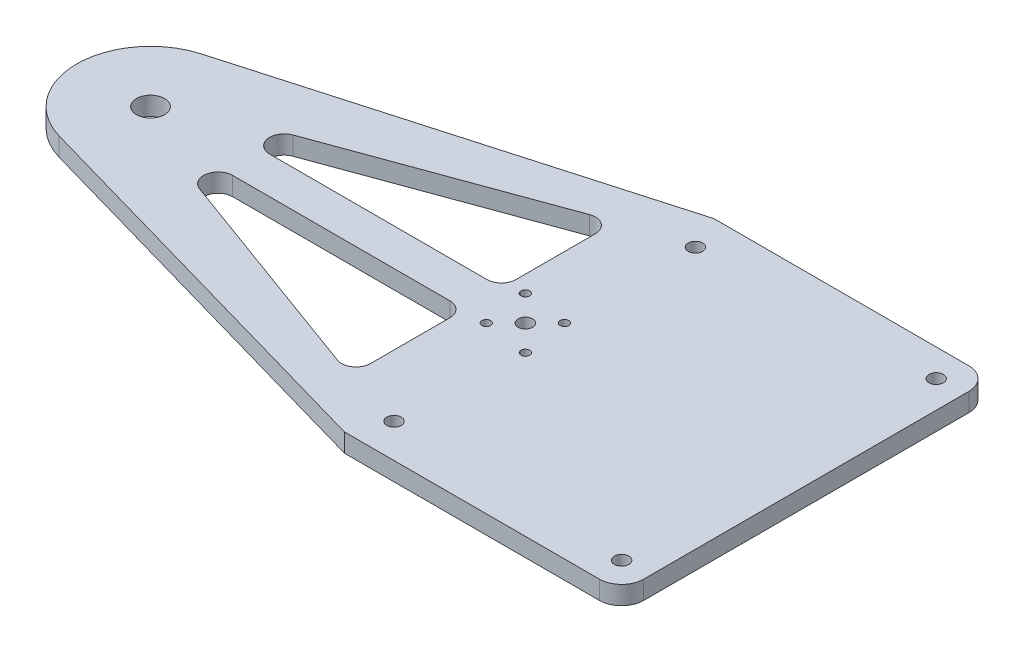
SolidWorks part; units mm, degrees
material "UHMW"
ref_plane "Front Plane" through (0, 0, 0) normal (0, 0, 1) x (1, 0, 0)
ref_plane "Top Plane" through (0, 0, 0) normal (0, 1, 0) x (1, 0, 0)
ref_plane "Right Plane" through (0, 0, 0) normal (1, 0, 0) x (0, 0, -1)
sketch "Sketch1" plane through (0, 0, 0) normal (0, 1, 0) x (1, 0, 0)
  line L0 (-47.625, 0) -> (47.625, 0) construction
  line L1 (-47.625, -63.5) -> (47.625, -63.5)
  line L2 (-47.625, -63.5) -> (-47.625, 63.5)
  line L3 (-47.625, 63.5) -> (47.625, 63.5)
  line L4 (47.625, -63.5) -> (47.625, 63.5)
  line L5 (-47.625, -63.5) -> (47.625, 63.5) construction
  line L6 (-47.625, 63.5) -> (47.625, -63.5) construction
  point P0 (0, 0)
  dimension "D1" = 95.25
  dimension "D2" = 127
  dimension "D3" = 63.5
extrude "Boss-Extrude1" add sketch "Sketch1" along normal blind 6.35
sketch "Sketch4" plane through (0, 6.35, 0) normal (0, 1, 0) x (1, 0, 0)
  line L1 (-47.625, 63.5) -> (-184.7599, 24.4278)
  line L5 (-47.625, 63.5) -> (-47.625, -63.5) construction
  line L9 (-47.625, -63.5) -> (-184.7599, -24.4278)
  line L10 (-47.625, 63.5) -> (-47.625, -63.5)
  arc A0 (-184.7599, 24.4278) -> (-184.7599, -24.4278) centre (-177.8, 0) ccw
  dimension "D1" = 50.8
  dimension "D2" = 177.8
extrude "Boss-Extrude3" add sketch "Sketch4" against normal blind 6.35
sketch "Sketch5" plane through (0, 6.35, 0) normal (0, 1, 0) x (1, 0, 0)
  line L0 (-48.9458, 0) -> (-31.7264, 0) construction
  line L3 (-48.9458, 0) -> (-91.3931, 0) construction
  circle A0 centre (-177.8, 0) radius 4.826
  circle A1 centre (-48.9458, 0) radius 2.5
  arc A2 (-184.7599, 24.4278) -> (-184.7599, -24.4278) centre (-177.8, 0) ccw construction
  arc A3 (-184.7599, 24.4278) -> (-184.7599, -24.4278) centre (-177.8, 0) ccw
  circle A4 centre (-42.2283, 6.7175) radius 1.5
  circle A5 centre (-57.7846, 8.8388) radius 1.5
  circle A6 centre (-40.107, -8.8388) radius 1.5
  circle A7 centre (-55.6633, -6.7175) radius 1.5
  circle A8 centre (-57.7846, 8.8388) radius 1.5 construction
  circle A9 centre (-55.6633, -6.7175) radius 1.5 construction
  circle A10 centre (-40.107, -8.8388) radius 1.5 construction
  circle A11 centre (-42.2283, 6.7175) radius 1.5 construction
  circle A12 centre (-48.9458, 0) radius 2.5 construction
  point P17 (-58.6463, -10.178)
  point P20 (-48.9458, 0)
  point P26 (-36.6924, 8.2175)
  dimension "D1" = 9.652
extrude "Cut-Extrude1" cut sketch "Sketch5" against normal through all contours A0 | A1 | A5 | A6 | A7 | A4 region at (-177.8, 6.35, 0) region at (-48.9458, 6.35, 0)
sketch "Sketch6" plane through (0, 6.35, 0) normal (0, 1, 0) x (1, 0, 0)
  line L0 (-63.5, 6.35) -> (-63.5, -6.35) construction
  line L1 (-63.5, 45.7715) -> (-171.45, 6.35)
  line L2 (-171.45, 6.35) -> (-63.5, 6.35)
  line L3 (-63.5, 6.35) -> (-63.5, 45.7715)
  line L4 (-63.5, -6.35) -> (-63.5, -45.7715)
  line L5 (-63.5, -45.7715) -> (-171.45, -6.35)
  line L6 (-171.45, -6.35) -> (-63.5, -6.35)
  line L7 (0, 0) -> (-63.5, 0) construction
  line L8 (-203.2, 75.5498) -> (-203.2, -75.5498) construction
  line L9 (-47.625, 63.5) -> (-184.7599, 24.4278) construction
  arc A0 (-184.7599, 24.4278) -> (-184.7599, -24.4278) centre (-177.8, 0) ccw construction
  point P2 (0, 0)
  point P12 (-203.2, 0)
  dimension "D1" = 31.75
  dimension "D2" = 12.7
  dimension "D3" = 12.7
  dimension "D4" = 63.5
extrude "Cut-Extrude2" cut sketch "Sketch6" against normal through all
fillet "Fillet9" radius 5 6 edges at (-171.45, 3.175, 6.35) (-63.5, 3.175, 6.35) (-63.5, 3.175, 45.7715) (-63.5, 3.175, -6.35) (-171.45, 3.175, -6.35) (-63.5, 3.175, -45.7715)
fillet "Fillet10" radius 7.62 2 edges at (47.625, 3.175, -63.5) (47.625, 3.175, 63.5)
sketch "Sketch7" plane through (0, 6.35, 0) normal (0, 1, 0) x (1, 0, 0)
  circle A0 centre (-42.2861, -51.8111) radius 2.4892
  circle A1 centre (-42.2861, 51.8111) radius 2.4892
  circle A2 centre (38.2023, 54.0773) radius 2.4892
  circle A3 centre (38.2023, -54.0773) radius 2.4892
extrude "Cut-Extrude3" cut sketch "Sketch7" against normal through all
